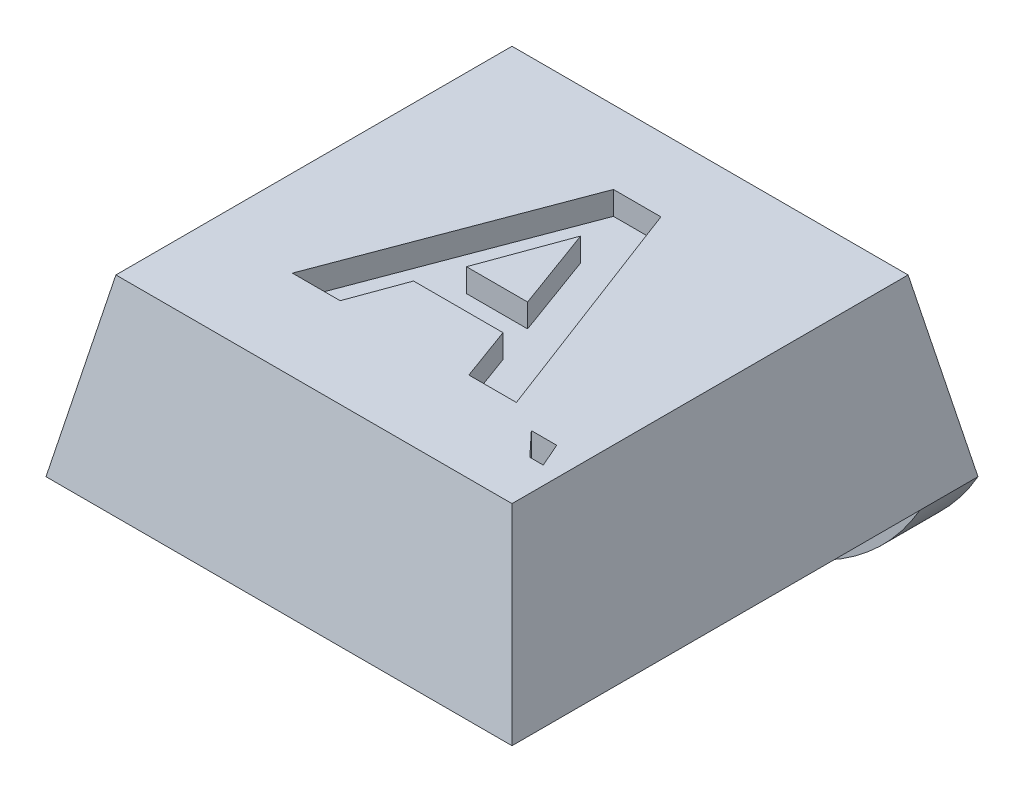
SolidWorks part; units mm, degrees
ref_plane "Front Plane" through (0, 0, 0) normal (0, 0, 1) x (1, 0, 0)
ref_plane "Top Plane" through (0, 0, 0) normal (0, 1, 0) x (1, 0, 0)
ref_plane "Right Plane" through (0, 0, 0) normal (1, 0, 0) x (0, 0, -1)
sketch "Sketch1" plane through (0, 0, 0) normal (0, 1, 0) x (1, 0, 0)
  line L1 (0, 0) -> (8, 0)
  line L2 (0, 0) -> (0, 8)
  line L3 (0, 8) -> (8, 8)
  line L4 (8, 0) -> (8, 8)
  dimension "D1" = 8
  dimension "D2" = 8
extrude "Boss-Extrude1" add sketch "Sketch1" along normal blind 3
sketch "Sketch2" plane through (0, 0, 0) normal (0, 0, 1) x (1, 0, 0)
  line L0 (0, 0) -> (0.6, 3)
  line L1 (0, 3) -> (8, 3) construction
  line L2 (0.6, 3) -> (0, 3)
  line L3 (0, 3) -> (0, 0)
  line L4 (8, 0) -> (7.4, 3)
  line L5 (7.4, 3) -> (8, 3)
  line L6 (8, 3) -> (8, 0)
  dimension "D1" = 0.6
  dimension "D2" = 0.6
extrude "Cut-Extrude1" cut sketch "Sketch2" against normal through all both and the other way through all
sketch "Sketch3" plane through (0, 0, 0) normal (1, 0, 0) x (0, 0, -1)
  line L0 (0, 0) -> (0.6, 3)
  line L1 (8, 3) -> (0, 3) construction
  line L2 (0.6, 3) -> (0, 3)
  line L3 (0, 3) -> (0, 0)
  line L4 (8, 3) -> (7.4, 3)
  line L5 (7.4, 3) -> (8, 0)
  line L6 (8, 3) -> (8, 0)
  dimension "D1" = 0.6
  dimension "D2" = 0.6
extrude "Cut-Extrude2" cut sketch "Sketch3" along normal blind 11
sketch "Sketch4" plane through (0, 0, 0) normal (0, -1, 0) x (1, 0, 0)
  line L0 (8, 0) -> (8, -8) construction
  line L3 (0, 0) -> (8, 0) construction
  circle A0 centre (4, -3.75) radius 1.75
  dimension "D1" = 3.5
  dimension "D2" = 4
  dimension "D3" = 3.75
extrude "Cut-Extrude3" cut sketch "Sketch4" against normal blind 0.4
sketch "Sketch5" plane through (0, 0, 0) normal (0, -1, 0) x (1, 0, 0)
  line L0 (8, 0) -> (8, -8) construction
  line L1 (0, -8) -> (8, -8)
  line L2 (0, -8) -> (0, -7)
  line L3 (0, -7) -> (8, -7)
  line L4 (8, -8) -> (8, -7)
  dimension "D1" = 1
extrude "Boss-Extrude2" add sketch "Sketch5" along normal blind 2
fillet "Fillet1" radius 4 2 edges at (8, -2, -7.5) (0, -2, -7.5)
sketch "Sketch6" plane through (0, 3, 0) normal (0, 1, 0) x (1, 0, 0)
  text T0 "A" font "Arial" height 4
extrude "Cut-Extrude4" cut sketch "Sketch6" against normal blind 0.4
sketch "Sketch7" plane through (0, 3, 0) normal (0, 1, 0) x (1, 0, 0)
  text T0 "`" font "Arial" height 2
extrude "Cut-Extrude5" cut sketch "Sketch7" against normal blind 0.5
